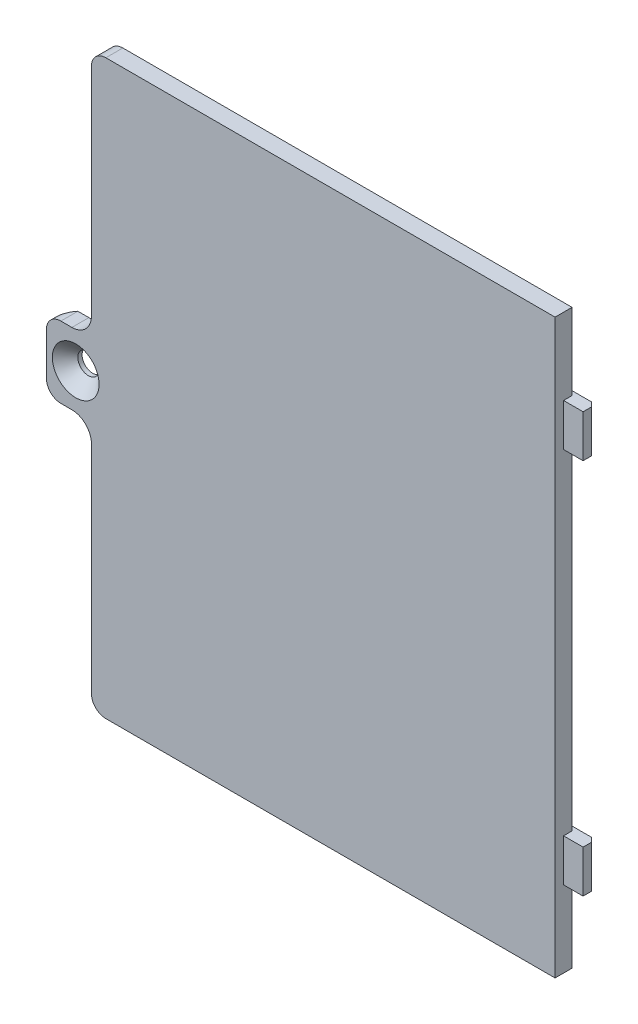
SolidWorks part; units mm, degrees
ref_plane "Front Plane" through (0, 0, 0) normal (0, 0, 1) x (1, 0, 0)
ref_plane "Top Plane" through (0, 0, 0) normal (0, 1, 0) x (1, 0, 0)
ref_plane "Right Plane" through (0, 0, 0) normal (1, 0, 0) x (0, 0, -1)
sketch "Sketch1" plane through (0, 0, 0) normal (0, 0, 1) x (1, 0, 0)
  line L125 (67.3, -33.7) -> (112.5, -33.7)
  line L126 (65.6, -6.5) -> (65.6, -32)
  line L127 (62, -4.2) -> (63.3, -4.2)
  line L128 (60.3, 2.5) -> (60.3, -2.5)
  line L129 (63.3, 4.2) -> (62, 4.2)
  line L130 (65.6, 32) -> (65.6, 6.5)
  line L131 (112.5, 33.7) -> (67.3, 33.7)
  line L141 (112.5, -33.7) -> (120.2, -33.7)
  line L142 (120.2, -33.7) -> (120.2, 33.7)
  line L143 (120.2, 33.7) -> (112.5, 33.7)
  arc A84 (65.6, -32) -> (67.3, -33.7) centre (67.3, -32) ccw
  arc A85 (65.6, -6.5) -> (63.3, -4.2) centre (63.3, -6.5) ccw
  arc A86 (60.3, -2.5) -> (62, -4.2) centre (62, -2.5) ccw
  arc A87 (62, 4.2) -> (60.3, 2.5) centre (62, 2.5) ccw
  arc A88 (63.3, 4.2) -> (65.6, 6.5) centre (63.3, 6.5) ccw
  arc A89 (67.3, 33.7) -> (65.6, 32) centre (67.3, 32) ccw
extrude "Boss-Extrude1" add sketch "Sketch1" along normal blind 1
sketch "Sketch2" plane through (0, 0, 0) normal (0, 0, -1) x (-1, 0, 0)
  line L8 (-67.3, 32.7) -> (-119.2, 32.7)
  line L9 (-119.2, 32.7) -> (-119.2, -32.7)
  line L10 (-119.2, -32.7) -> (-67.3, -32.7)
  line L11 (-66.6, -32) -> (-66.6, -6.5)
  line L12 (-66.6, 6.5) -> (-66.6, -6.5)
  line L15 (-66.6, 6.5) -> (-66.6, 32)
  line L16 (-67.3, 33.7) -> (-120.2, 33.7)
  line L17 (-120.2, 33.7) -> (-120.2, -33.7)
  line L18 (-120.2, -33.7) -> (-67.3, -33.7)
  line L19 (-65.6, -32) -> (-65.6, -6.5)
  line L20 (-63.3, -4.2) -> (-62, -4.2)
  line L21 (-60.3, -2.5) -> (-60.3, 2.5)
  line L22 (-62, 4.2) -> (-63.3, 4.2)
  line L23 (-65.6, 6.5) -> (-65.6, 32)
  line L24 (-67.3, 33.7) -> (-120.2, 33.7)
  line L25 (-120.2, 33.7) -> (-120.2, -33.7)
  line L26 (-120.2, -33.7) -> (-67.3, -33.7)
  line L27 (-65.6, -32) -> (-65.6, -6.5)
  line L28 (-63.3, -4.2) -> (-62, -4.2)
  line L29 (-60.3, -2.5) -> (-60.3, 2.5)
  line L30 (-62, 4.2) -> (-63.3, 4.2)
  line L31 (-65.6, 6.5) -> (-65.6, 32)
  line L32 (-62, 3.2) -> (-63.3, 3.2) construction
  line L33 (-61.3, -2.5) -> (-61.3, 2.5) construction
  line L34 (-63.3, -3.2) -> (-62, -3.2) construction
  arc A6 (-67.3, -32.7) -> (-66.6, -32) centre (-67.3, -32) ccw
  arc A11 (-66.6, 32) -> (-67.3, 32.7) centre (-67.3, 32) ccw
  arc A12 (-67.3, -33.7) -> (-65.6, -32) centre (-67.3, -32) ccw
  arc A13 (-63.3, -4.2) -> (-65.6, -6.5) centre (-63.3, -6.5) ccw
  arc A14 (-62, -4.2) -> (-60.3, -2.5) centre (-62, -2.5) ccw
  arc A15 (-60.3, 2.5) -> (-62, 4.2) centre (-62, 2.5) ccw
  arc A16 (-65.6, 6.5) -> (-63.3, 4.2) centre (-63.3, 6.5) ccw
  arc A17 (-65.6, 32) -> (-67.3, 33.7) centre (-67.3, 32) ccw
  arc A18 (-67.3, -33.7) -> (-65.6, -32) centre (-67.3, -32) ccw
  arc A19 (-63.3, -4.2) -> (-65.6, -6.5) centre (-63.3, -6.5) ccw
  arc A20 (-62, -4.2) -> (-60.3, -2.5) centre (-62, -2.5) ccw
  arc A21 (-60.3, 2.5) -> (-62, 4.2) centre (-62, 2.5) ccw
  arc A22 (-65.6, 6.5) -> (-63.3, 4.2) centre (-63.3, 6.5) ccw
  arc A23 (-65.6, 32) -> (-67.3, 33.7) centre (-67.3, 32) ccw
  arc A24 (-66.6, 6.5) -> (-63.3, 3.2) centre (-63.3, 6.5) ccw construction
  arc A25 (-62, -3.2) -> (-61.3, -2.5) centre (-62, -2.5) ccw construction
  arc A26 (-63.3, -3.2) -> (-66.6, -6.5) centre (-63.3, -6.5) ccw construction
  arc A27 (-61.3, 2.5) -> (-62, 3.2) centre (-62, 2.5) ccw construction
  dimension "D1" = 0
  dimension "D2" = 1
extrude "Boss-Extrude2" add sketch "Sketch2" along normal blind 1
sketch "Sketch3" plane through (0, 4.2, 0) normal (0, 1, 0) x (1, 0, 0)
  line L0 (62, 1) -> (60.3, -1)
  line L1 (60.3, -1) -> (60.3, 1)
  line L2 (60.3, 1) -> (62, 1)
extrude "Cut-Extrude1" cut sketch "Sketch3" against normal up to surface (8.4 mm away) up to face at (62.65, -4.2, 0)
sketch "Sketch4" plane through (0, 0, -1) normal (0, 0, -1) x (-1, 0, 0)
  circle A0 centre (-63.75, 0) radius 1.25
  dimension "D1" = 2.5
extrude "Cut-Extrude2" cut sketch "Sketch4" against normal up to next
chamfer "Chamfer1" distance 1.5 angle 45 1 edges at (65, 0, 1)
sketch "Sketch5" plane through (0, 0, 0) normal (0, 0, -1) x (-1, 0, 0)
  line L0 (-66.6, 0) -> (-119.2, 0) construction
  line L1 (-66.6, -32) -> (-66.6, 32) construction
  line L2 (-119.2, 32.7) -> (-119.2, -32.7) construction
  line L3 (-120.2, 33.7) -> (-120.2, -33.7) construction
  line L4 (-66.6, -19.7) -> (-122.5, -19.7)
  line L5 (-66.6, -19.7) -> (-66.6, -24.7)
  line L6 (-66.6, -24.7) -> (-122.5, -24.7)
  line L7 (-122.5, -19.7) -> (-122.5, -24.7)
  line L8 (-122.5, 19.7) -> (-122.5, 24.7)
  line L9 (-66.6, 19.7) -> (-122.5, 19.7)
  line L10 (-66.6, 24.7) -> (-122.5, 24.7)
  line L11 (-66.6, 19.7) -> (-66.6, 24.7)
  dimension "D1" = 5
  dimension "D2" = 2.3
  dimension "D3" = 39.4
extrude "Boss-Extrude3" add sketch "Sketch5" along normal blind 1.5
chamfer "Chamfer3" distance 0.5 angle 45 4 edges at (122.5, 22.2, -1.5) (122.5, -22.2, -1.5) (66.6, -22.2, -1.5) (66.6, 22.2, -1.5)
